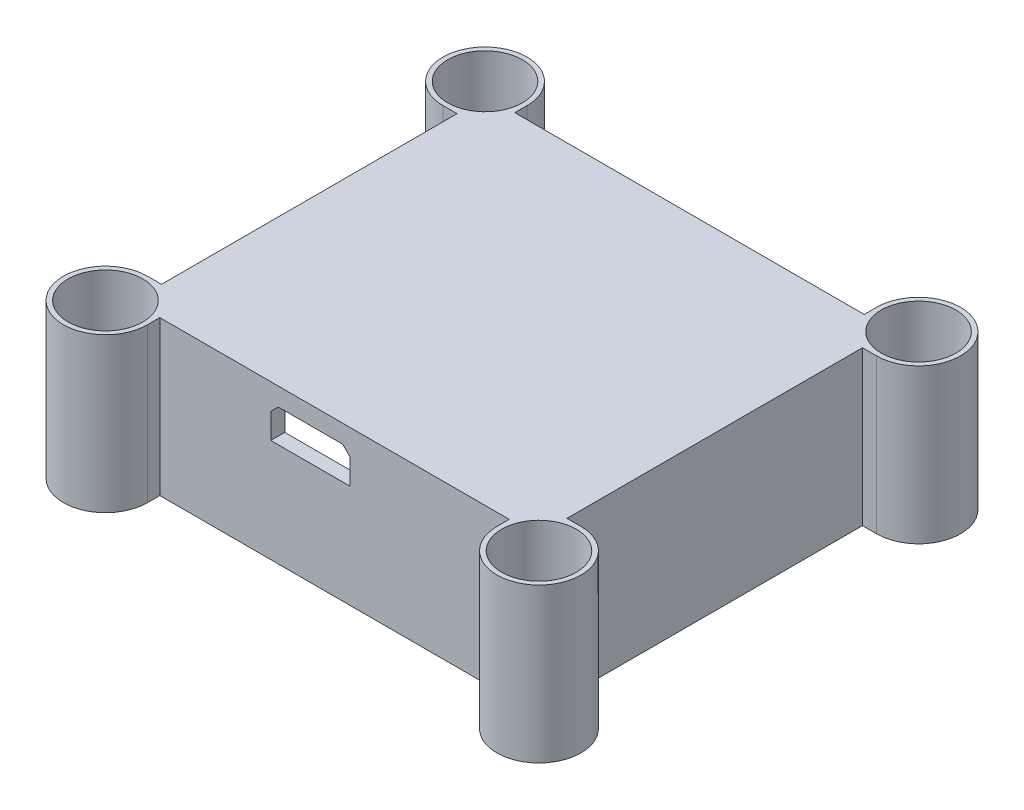
SolidWorks part; units mm, degrees
ref_plane "Front Plane" through (0, 0, 0) normal (0, 0, 1) x (1, 0, 0)
ref_plane "Top Plane" through (0, 0, 0) normal (0, 1, 0) x (1, 0, 0)
ref_plane "Right Plane" through (0, 0, 0) normal (1, 0, 0) x (0, 0, -1)
sketch "Sketch1" plane through (0, 0, 0) normal (0, 1, 0) x (1, 0, 0)
  line L0 (-20.2, 17.5) -> (-21.7, 17.5) construction
  line L1 (-20.2, 17.5) -> (20.2, 17.5)
  line L2 (-20.2, 17.5) -> (-20.2, -17.5)
  line L3 (-20.2, -17.5) -> (20.2, -17.5)
  line L4 (20.2, 17.5) -> (20.2, -17.5)
  line L5 (-20.2, 17.5) -> (20.2, -17.5) construction
  line L6 (-20.2, -17.5) -> (20.2, 17.5) construction
  line L7 (-20.2, 17.5) -> (20.2, 17.5)
  line L8 (-20.2, 17.5) -> (-20.2, 27.5)
  line L9 (-20.2, 27.5) -> (20.2, 27.5)
  line L10 (20.2, 17.5) -> (20.2, 27.5)
  line L11 (21.7, -19) -> (-21.7, -19)
  line L12 (21.7, -19) -> (21.7, 19)
  line L13 (21.7, 19) -> (-21.7, 19)
  line L14 (-21.7, -19) -> (-21.7, 19)
  line L15 (21.7, -19) -> (-21.7, 19) construction
  line L16 (21.7, 19) -> (-21.7, -19) construction
  line L17 (-20.2, 17.5) -> (-20.2, 19) construction
  line L18 (-23.2047, 15.8175) -> (-21.7, 15.8175)
  line L19 (-18.7047, 20.3175) -> (-18.7047, 19)
  line L20 (0, 19) -> (0, -19) construction
  line L21 (-21.7, 0) -> (21.7, 0) construction
  line L22 (18.7047, 20.3175) -> (18.7047, 19)
  line L23 (23.2047, 15.8175) -> (21.7, 15.8175)
  line L24 (18.7047, -20.3175) -> (18.7047, -19)
  line L25 (23.2047, -15.8175) -> (21.7, -15.8175)
  line L26 (-18.7047, -20.3175) -> (-18.7047, -19)
  line L27 (-23.2047, -15.8175) -> (-21.7, -15.8175)
  circle A0 centre (-23.2047, 20.3175) radius 2
  circle A1 centre (-23.2047, 20.3175) radius 4.5
  circle A2 centre (23.2047, 20.3175) radius 4.5
  circle A3 centre (23.2047, 20.3175) radius 2
  circle A4 centre (-23.2047, -20.3175) radius 2
  circle A5 centre (23.2047, -20.3175) radius 2
  circle A6 centre (23.2047, -20.3175) radius 4.5
  circle A7 centre (-23.2047, -20.3175) radius 4.5
  point P0 (0, 0)
  point P9 (0, 0)
  dimension "D5" = 4
  dimension "D6" = 9
  dimension "D1" = 40.4
  dimension "D2" = 35
  dimension "D3" = 10
  dimension "D4" = 1.5
extrude "Boss-Extrude1" add sketch "Sketch1" along normal blind 15 contours A7 L11 A4 L14 | L27 A7 L14 | A7 L14 L11 L3 L2 | L11 A7 L26 | L3 A7 L11 A6 | L14 A7 L2 A1 | A1 L14 A0 L13 L8 | L13 A1 L8 | L14 A1 L2 L8 L13 | L1 A1 L13 L8 | A1 L18 L14 | A1 L13 L19 | L7 A2 L13 A1 | L13 A3 L12 A2 L10 | L13 A2 L22 | A2 L1 L10 L13 | A2 L12 L13 L10 L4 | L23 A2 L12 | A6 L12 A2 L4 | A2 L13 L10 | L12 A6 L4 L3 L11 | A6 L25 L12 | A6 L12 A5 L11 | A6 L11 L24 region at (-19.6918, 0, -18.3522) region at (-20.9933, 0, -17.715) region at (0, 0, -18.2449) region at (-20.9433, 0, 0) region at (-20.95, 0, -19.1172) region at (-19.5542, 0, -20.9266) region at (19.6918, 0, -18.3522) region at (-18.7637, 0, -19.3279) region at (-20.6362, 0, 17.8898) region at (-22.074, 0, -15.8948) region at (20.9933, 0, -17.715) region at (19.5542, 0, -20.9266) region at (18.7637, 0, -19.3279) region at (20.9433, 0, 0) region at (0, 0, 18.2449) region at (-22.074, 0, 15.8948) region at (-21.8273, 0, 17.5383) region at (20.3172, 0, -21.3337) region at (20.6362, 0, 17.8898) region at (22.074, 0, -15.8948) region at (-18.7637, 0, 19.3279) region at (22.4629, 0, 16.0082) region at (22.074, 0, 15.8948) region at (18.7637, 0, 19.3279)
sketch "Sketch2" plane through (0, 15, 0) normal (0, 1, 0) x (1, 0, 0)
  line L12 (-21.7, 15.8175) -> (-21.7, -15.8175)
  line L13 (-21.7, -15.8175) -> (-23.2047, -15.8175)
  line L14 (-18.7047, -20.3175) -> (-18.7047, -19)
  line L15 (-18.7047, -19) -> (18.7047, -19)
  line L16 (18.7047, -19) -> (18.7047, -20.3175)
  line L17 (23.2047, -15.8175) -> (21.7, -15.8175)
  line L18 (21.7, -15.8175) -> (21.7, 15.8175)
  line L19 (21.7, 15.8175) -> (23.2047, 15.8175)
  line L20 (18.7047, 20.3175) -> (18.7047, 19)
  line L21 (18.7047, 19) -> (-18.7047, 19)
  line L22 (-18.7047, 19) -> (-18.7047, 20.3175)
  line L23 (-23.2047, 15.8175) -> (-21.7, 15.8175)
  line L24 (-21.7, 15.8175) -> (-21.7, -15.8175)
  line L25 (-21.7, -15.8175) -> (-23.2047, -15.8175)
  line L26 (-18.7047, -20.3175) -> (-18.7047, -19)
  line L27 (-18.7047, -19) -> (18.7047, -19)
  line L28 (18.7047, -19) -> (18.7047, -20.3175)
  line L29 (23.2047, -15.8175) -> (21.7, -15.8175)
  line L30 (21.7, -15.8175) -> (21.7, 15.8175)
  line L31 (21.7, 15.8175) -> (23.2047, 15.8175)
  line L32 (18.7047, 20.3175) -> (18.7047, 19)
  line L33 (18.7047, 19) -> (-18.7047, 19)
  line L34 (-18.7047, 19) -> (-18.7047, 20.3175)
  line L35 (-23.2047, 15.8175) -> (-21.7, 15.8175)
  circle A0 centre (23.2047, -20.3175) radius 2 construction
  circle A1 centre (23.2047, 20.3175) radius 2 construction
  circle A2 centre (-23.2047, 20.3175) radius 2 construction
  circle A3 centre (-23.2047, -20.3175) radius 2 construction
  arc A4 (-23.2047, -15.8175) -> (-18.7047, -20.3175) centre (-23.2047, -20.3175) ccw
  arc A5 (18.7047, -20.3175) -> (23.2047, -15.8175) centre (23.2047, -20.3175) ccw
  arc A6 (23.2047, 15.8175) -> (18.7047, 20.3175) centre (23.2047, 20.3175) ccw
  arc A7 (-18.7047, 20.3175) -> (-23.2047, 15.8175) centre (-23.2047, 20.3175) ccw
  arc A8 (-23.2047, -15.8175) -> (-18.7047, -20.3175) centre (-23.2047, -20.3175) ccw
  arc A9 (18.7047, -20.3175) -> (23.2047, -15.8175) centre (23.2047, -20.3175) ccw
  arc A10 (23.2047, 15.8175) -> (18.7047, 20.3175) centre (23.2047, 20.3175) ccw
  arc A11 (-18.7047, 20.3175) -> (-23.2047, 15.8175) centre (-23.2047, 20.3175) ccw
  circle A12 centre (23.2047, -20.3175) radius 2
  circle A13 centre (23.2047, 20.3175) radius 2
  circle A14 centre (-23.2047, 20.3175) radius 2
  circle A15 centre (-23.2047, -20.3175) radius 2
  dimension "D1" = 0
extrude "Boss-Extrude2" add sketch "Sketch2" along normal blind 1.5
sketch "Sketch3" plane through (0, 16.5, 0) normal (0, 1, 0) x (1, 0, 0)
  circle A0 centre (-23.2047, -20.3175) radius 4
  arc A1 (-23.2047, -15.8175) -> (-18.7047, -20.3175) centre (-23.2047, -20.3175) ccw construction
  circle A2 centre (-23.2047, 20.3175) radius 4
  circle A3 centre (23.2047, 20.3175) radius 4
  circle A4 centre (23.2047, -20.3175) radius 4
  dimension "D1" = 0.5
extrude "Cut-Extrude1" cut sketch "Sketch3" against normal offset from surface (15 mm away) 1.5 up to face at (0, 0, 0)
sketch "Sketch4" plane through (0, 15, 0) normal (0, -1, 0) x (1, 0, 0)
  line L0 (-20.2, 17.5) -> (20.2, 17.5) construction
  line L1 (-7.2, 17.5) -> (2.05, 17.5)
  line L2 (-7.2, 17.5) -> (-7.2, 13.7)
  line L3 (-7.2, 13.7) -> (2.05, 13.7)
  line L4 (2.05, 17.5) -> (2.05, 13.7)
  line L5 (-7.2, 13.7) -> (-20.2, 13.7)
  line L6 (-20.2, -17.5) -> (-20.2, 17.5) construction
  line L7 (2.05, 13.7) -> (20.2, 13.7)
  line L8 (20.2, 17.5) -> (20.2, -17.5) construction
  line L9 (-20.2, -17.5) -> (-20.2, 17.5) construction
  line L10 (-20.2, -17.5) -> (20.2, -17.5) construction
  line L11 (-20.2, -17.5) -> (-17.2, -17.5)
  line L12 (-20.2, -17.5) -> (-20.2, -14.5)
  line L13 (-20.2, -14.5) -> (-17.2, -14.5)
  line L14 (-17.2, -17.5) -> (-17.2, -14.5)
  line L15 (14.45, -17.5) -> (11.95, -17.5)
  line L16 (14.45, -17.5) -> (14.45, -15.5)
  line L17 (14.45, -15.5) -> (11.95, -15.5)
  line L18 (11.95, -17.5) -> (11.95, -15.5)
  line L19 (20.2, 17.5) -> (20.2, -17.5) construction
  point P14 (-7.2, 15.6)
  line M5 (20.2, 17.5) -> (-20.2, 17.5)
  line M6 (-20.2, 17.5) -> (-20.2, -17.5)
  line M7 (-20.2, -17.5) -> (20.2, -17.5)
  line M8 (20.2, -17.5) -> (20.2, 17.5)
  dimension "D1" = 9.25
  dimension "D2" = 3.8
  dimension "D3" = 13
  dimension "D4" = 3
  dimension "D5" = 5.75
  dimension "D6" = 2.5
  dimension "D7" = 2
extrude "Boss-Extrude3" add sketch "Sketch4" along normal blind 1.1 contours L5 L2 M5 M6 | L14 L13 M7 M6 | L4 L7 M8 M5 | L18 L16 L17 M7 region at (-13.7, 15, 15.6) region at (11.125, 15, 15.6) region at (-18.7, 15, -16) region at (13.2, 15, -16.5)
sketch "Sketch5" plane through (0, 13.9, 0) normal (0, -1, 0) x (1, 0, 0)
  line L1 (-17.2, -17.5) -> (-20.2, -17.5)
  line L2 (-17.2, -17.5) -> (-17.2, -14)
  line L3 (-17.2, -14) -> (-20.2, -14)
  line L4 (-20.2, -17.5) -> (-20.2, -14)
  line L5 (-20.2, -14.5) -> (-17.2, -14.5) construction
  line L6 (11.95, -17.5) -> (11.95, -15.5) construction
  line L7 (14.45, -17.5) -> (11.95, -17.5)
  line L8 (14.45, -17.5) -> (14.45, -15)
  line L9 (14.45, -15) -> (11.95, -15)
  line L10 (11.95, -17.5) -> (11.95, -15)
  line L11 (-18.7, -14) -> (-18.7, -14.5) construction
  line L12 (13.2, -15) -> (13.2, -15.5) construction
  line L13 (14.45, -15.5) -> (11.95, -15.5) construction
  line L14 (-13.7, 17.5) -> (-13.7, 13.7) construction
  line L15 (-7.2, 17.5) -> (-20.2, 17.5) construction
  line L16 (-7.2, 13.7) -> (-20.2, 13.7) construction
  line L17 (-20.2, 17.5) -> (20.2, 17.5) construction
  line L18 (-15.2, 17.5) -> (-12.2, 17.5)
  line L19 (-15.2, 17.5) -> (-15.2, 13.2)
  line L20 (-15.2, 13.2) -> (-12.2, 13.2)
  line L21 (-12.2, 17.5) -> (-12.2, 13.2)
  line L22 (-15.2, 17.5) -> (-12.2, 13.2) construction
  line L23 (-15.2, 13.2) -> (-12.2, 17.5) construction
  line L24 (-13.7, 13.7) -> (-13.7, 13.2) construction
  line L25 (11.125, 17.5) -> (11.125, 13.7) construction
  line L26 (20.2, 17.5) -> (2.05, 17.5) construction
  line L27 (2.05, 13.7) -> (20.2, 13.7) construction
  line L28 (11.125, 13.7) -> (11.125, 13.2) construction
  line L29 (9.625, 17.5) -> (12.625, 17.5)
  line L30 (9.625, 17.5) -> (9.625, 13.2)
  line L31 (9.625, 13.2) -> (12.625, 13.2)
  line L32 (12.625, 17.5) -> (12.625, 13.2)
  line L33 (9.625, 17.5) -> (12.625, 13.2) construction
  line L34 (9.625, 13.2) -> (12.625, 17.5) construction
  line L35 (-20.2, -17.5) -> (-17.2, -17.5) construction
  point P5 (0, 0)
  point P6 (-20.2, -12.45)
  point P28 (-13.7, 15.35)
  point P42 (11.125, 15.35)
  point P47 (0, 0)
  point P49 (0, 0)
  point P50 (0, 0)
  dimension "D1" = 0.5
  dimension "D2" = 3
extrude "Boss-Extrude4" add sketch "Sketch5" along normal blind 1
chamfer "Chamfer1" distance 0.5 angle 45 2 edges at (-18.7, 12.9, -14) (13.2, 12.9, -15)
sketch "Sketch6" plane through (0, 0, 17.5) normal (0, 0, -1) x (-1, 0, 0)
  line L0 (7.2, 15) -> (-2.05, 15) construction
  line L1 (2.575, 15) -> (2.575, 0) construction
  line L2 (20.2, 0) -> (-20.2, 0) construction
  line L4 (-1.675, 11.05) -> (6.825, 11.05)
  line L5 (-1.675, 11.05) -> (-1.675, 14.55)
  line L6 (-1.675, 14.55) -> (6.825, 14.55)
  line L7 (6.825, 11.05) -> (6.825, 14.55)
  line L8 (-1.675, 11.05) -> (6.825, 14.55) construction
  line L9 (-1.675, 14.55) -> (6.825, 11.05) construction
  point P6 (2.575, 12.8)
  dimension "D1" = 8.5
  dimension "D2" = 3.5
  dimension "D3" = 3.95
extrude "Cut-Extrude2" cut sketch "Sketch6" against normal up to next
chamfer "Chamfer2" distance 0.8 angle 45 2 edges at (-6.825, 14.55, 18.25) (1.675, 14.55, 18.25)
fillet "Fillet1" radius 2 4 edges at (20.2, 7.5, -17.5) (-20.2, 6.45, -17.5) (-20.2, 6.95, 17.5) (20.2, 6.95, 17.5)
